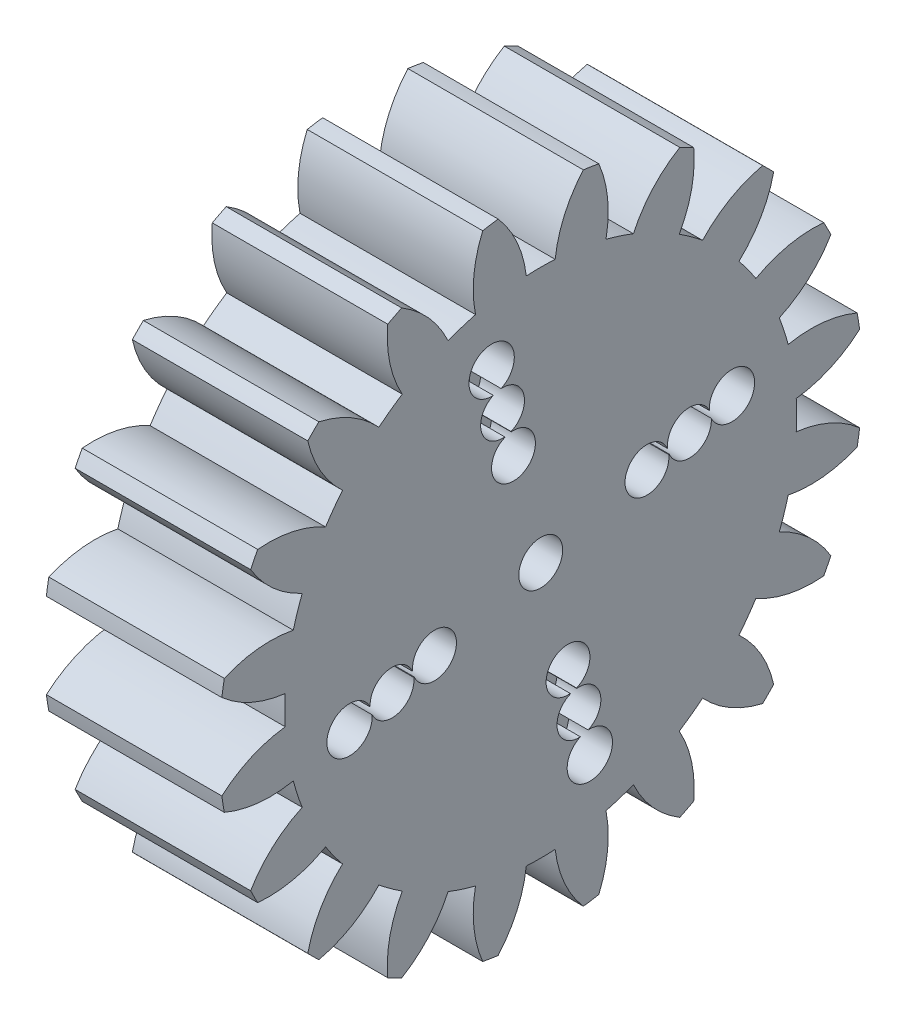
SolidWorks part; units mm, degrees
material "WhitePLA"
ref_plane "Plane1" through (0, 0, 0) normal (0, 0, 1) x (1, 0, 0)
ref_plane "Plane2" through (0, 0, 0) normal (0, 1, 0) x (1, 0, 0)
ref_plane "Plane3" through (0, 0, 0) normal (1, 0, 0) x (0, 0, -1)
sketch "HoldingSke" plane through (0, 0, 0) normal (0, 1, 0) x (1, 0, 0)
  line L0 (0, 0) -> (0.4698, -0.171)
  line L1 (-15, 0) -> (100, 0) construction
  line L2 (0, 0) -> (-2.1039, 2.3779)
  line L3 (0, 0) -> (-11.863, 4.5341)
  line L4 (0, 0) -> (8.1152, 2.9537)
  line L5 (0, 0) -> (-46.8476, -17.4728)
  line L6 (0, 0) -> (-9.9476, -6.7116)
  line L7 (-2.1039, 2.3779) -> (8.6586, 51.2059)
  line L8 (-76.2, 54.61) -> (-75.7, 54.61)
  line L9 (-71.009, 38.7566) -> (-53.1078, 45.2721)
  line L10 (-76.2, 71.12) -> (104.1128, 71.12)
  line L11 (0, 0) -> (-12, 0)
  line L12 (-76.2, 101.6) -> (-76.133, 101.6)
  line L13 (24.9733, 27.94) -> (52.9518, 28.4284)
  line L14 (24.9733, 27.94) -> (24.9743, 27.94)
  line L15 (24.9733, 27.94) -> (100.4006, 29.5858)
  line L16 (-63.627, -2) -> (-12.827, -2)
  circle A0 centre (0, 0) radius 1.5
  circle A1 centre (0, 0) radius 17.499
  circle A2 centre (0, 0) radius 37.5
  circle A3 centre (0, 0) radius 1.5
  dimension "Num_teeth" = 20
  dimension "Pitch_radius" = 180.3128
  dimension "Width" = 12
  dimension "Thickness" = 12
sketch "BasProSke" plane through (0, 0, 0) normal (0, 1, 0) x (1, 0, 0)
  line L0 (-10, 0) -> (60, 0) construction
  line L1 (0, 0) -> (0, 22)
  line L2 (0, 0) -> (12, 0)
  line L3 (12, 0) -> (12, 22)
  line L4 (12, 22) -> (0, 22)
  dimension "Thickness" = 12
  dimension "Diameter" = 44
revolve "Base-Revolve" add sketch "BasProSke" angle 360 about L0
sketch "TooCutSke" plane through (0, 0, 0) normal (1, 0, 0) x (0, 0, -1)
  line L1 (0, 0) -> (0, 107) construction
  line L2 (0, 0) -> (-1.6864, 19.9288) construction
  line L3 (0, 0) -> (-6.2409, 39.4033) construction
  line L4 (-1.6864, 19.9288) -> (-3.1204, 19.7016) construction
  arc A0 (0.9862, 17.4712) -> (-0.9862, 17.4712) centre (0, 0) ccw
  arc A1 (2.9329, 21.8293) -> (-2.9329, 21.8293) centre (0, 0) ccw
  circle A2 centre (0, 0) radius 20 construction
  circle A3 centre (0, 0) radius 18.7939 construction
  arc A4 (-0.9862, 17.4712) -> (-2.9329, 21.8293) centre (-8.9313, 16.536) ccw
  arc A5 (2.9329, 21.8293) -> (0.9862, 17.4712) centre (8.9313, 16.536) ccw
extrude "ToothCut" cut sketch "TooCutSke" along normal through all
fillet "Breaks" [suppressed] radius 0.04 tangent propagation no
fillet "RootFillets" [suppressed] radius 0.501
pattern_circular "TeethCuts" count 20 every 18 about axis through (-10, 0, 0) along (1, 0, 0) of "ToothCut", "RootFillets", "Breaks"
sketch "HubNeaOneSke" plane through (0, 0, 0) normal (-1, 0, 0) x (0, 0, 1)
  circle A0 centre (0, 0) radius 17.499
  dimension "Diameter" = 34.998
extrude "HubNearOne" [suppressed] add sketch "HubNeaOneSke" along normal blind 38.0001
sketch "HubNeaBotSke" plane through (0, 0, 0) normal (-1, 0, 0) x (0, 0, 1)
  circle A0 centre (0, 0) radius 17.499
  dimension "Diameter" = 34.998
extrude "HubNearBoth" [suppressed] add sketch "HubNeaBotSke" along normal blind 19
ref_plane "FarPln" through (12, 0, 0) normal (1, 0, 0) x (0, 0, -1)
sketch "HubFarSke" plane through (12, 0, 0) normal (1, 0, 0) x (0, 0, -1)
  circle A0 centre (0, 0) radius 17.499
  dimension "Diameter" = 34.998
extrude "HubFar" [suppressed] add sketch "HubFarSke" along normal blind 19
sketch "BorSke" plane through (0, 0, 0) normal (1, 0, 0) x (0, 0, -1)
  circle A0 centre (0, 0) radius 1.5
  dimension "Diameter" = 3
extrude "Bore" cut sketch "BorSke" along normal mid plane 100.0001
sketch "KeySke" plane through (0, 0, 0) normal (1, 0, 0) x (0, 0, -1)
  line L0 (-0.6, 0) -> (-0.6, 2)
  line L1 (-0.6, 2) -> (0.6, 2)
  line L2 (0.6, 2) -> (0.6, 0)
  line L3 (0, 0) -> (0, 34) construction
  line L4 (-0.6, 0) -> (0.6, 0)
extrude "Keyway" [suppressed] cut sketch "KeySke" along normal mid plane 100.0001
pattern_circular "Keyway2" [suppressed] count 2 every 90 about axis through (-10, 0, 0) along (1, 0, 0) reverse direction yes
sketch "Sketch1" plane through (12, 0, 0) normal (1, 0, 0) x (0, 0, -1)
  line L0 (-2.4602, 8.6778) -> (-2.4471, 8.6468)
  line L1 (-2.0331, 8.786) -> (-2.0207, 8.7563)
  circle A0 centre (3.3568, -13.076) radius 0.75
  circle A1 centre (2.6109, -10.1702) radius 0.75
  circle A2 centre (1.8649, -7.2644) radius 0.75
  circle A3 centre (-13.076, -3.3568) radius 0.75
  circle A4 centre (-10.1702, -2.6109) radius 0.75
  circle A5 centre (-7.2644, -1.8649) radius 0.75
  circle A6 centre (13.076, 3.3568) radius 0.75
  circle A7 centre (10.1702, 2.6109) radius 0.75
  circle A8 centre (7.2644, 1.8649) radius 0.75
  circle A9 centre (-1.8649, 7.2644) radius 0.75
  circle A10 centre (-2.6109, 10.1702) radius 0.75
  circle A11 centre (-3.3568, 13.076) radius 0.75
  circle A12 centre (0, 0) radius 14.25
  circle A13 centre (0, 0) radius 1.5
  arc A14 (-2.7112, 11.6669) -> (-3.2439, 11.5301) centre (-3.3568, 13.076) ccw
  arc A15 (-3.2439, 11.5301) -> (-2.4602, 8.6778) centre (-2.6109, 10.1702) ccw
  arc A16 (-2.4471, 8.6468) -> (-2.0207, 8.7563) centre (-1.8649, 7.2644) ccw
  arc A17 (-2.0331, 8.786) -> (-2.7112, 11.6669) centre (-2.6109, 10.1702) ccw
  circle A18 centre (0, 0) radius 22
  dimension "D1" = 3
  dimension "D2" = 28.5
  dimension "D3" = 1.5
  dimension "D29" = 3.1
  dimension "D30" = 3
  dimension "D33" = 44
  dimension "D4" = 4.3952
  dimension "D5" = 7.301
  dimension "D6" = 10.2067
  dimension "D7" = 14.1144
  dimension "D8" = 14.8603
  dimension "D9" = 15.6063
  dimension "D10" = 17.4712
  dimension "D11" = 19.3361
  dimension "D12" = 20.0821
  dimension "D13" = 20.828
  dimension "D14" = 24.7356
  dimension "D15" = 27.6414
  dimension "D16" = 30.5472
  dimension "D17" = 8.7303
  dimension "D18" = 11.6361
  dimension "D19" = 14.5419
  dimension "D20" = 18.4495
  dimension "D21" = 19.1955
  dimension "D22" = 19.9414
  dimension "D23" = 21.8063
  dimension "D24" = 23.6712
  dimension "D25" = 24.4172
  dimension "D26" = 25.1632
  dimension "D27" = 29.0708
  dimension "D28" = 31.9766
  dimension "D31" = 15.011
  dimension "D32" = 15.4381
  dimension "D35" = 20.3839
extrude "Cut-Extrude1" cut sketch "Sketch1" against normal up to surface (12 mm away) contours A11 | A10 | A7 | A6 | A5 | A4 | A2 | A0 | A9 | A8 | A3 | A1 region at (12, 13.076, 3.3568) region at (12, -13.076, -3.3568) region at (12, 3.3568, -13.076) region at (12, -7.2644, -1.8649) region at (12, -2.6109, 10.1702) region at (12, -1.8649, 7.2644) region at (12, 2.6109, -10.1702) region at (12, 10.1702, 2.6109) up to face at (0, 0, -1.5)
extrude "Cut-Extrude2" cut sketch "Sketch1<3>" against normal blind 3 contours L1 A17 A14 A12 A11 A15 L0 A16 A10 A9 | A12 A14 region at (12, 9.7979, 3.9659) region at (12, 14.1077, 3.6217)
sketch "Sketch1<3>" plane through (12, 0, 0) normal (1, 0, 0) x (0, 0, -1) same geometry as "Sketch1"
ref_axis "Axis1" through (12, 0, 0) along (1, 0, 0)
pattern_circular "CirPattern1" count 4 every 90 about axis through (12, 0, 0) along (1, 0, 0) of "Cut-Extrude2"
ref_axis "Axis2" through (12, 0, 0) along (1, 0, 0)
equation "' \"Module@HoldingSke\" = 6.35"
equation "' \"Num_teeth@HoldingSke\" = 12"
equation "' \"Ap@HoldingSke\" =  20"
equation "' \"Ap@HoldingSke\" = 20"
equation "' \"Width@HoldingSke\" = 0.5 * 25.4"
equation "' \"Hub_dia@HoldingSke\"= 1 * 25.4"
equation "' \"Hub_dia@HoldingSke\" = 1 * 25.4"
equation "' \"Overall_len@HoldingSke\" = 1.0 * 25.4"
equation "' \"Bore@HoldingSke\" = 0.75 * 25.4"
equation "' \"T_dim@HoldingSke\" = 0.1 * 25.4"
equation "' \"Width@KeySke\" = 0.25 * 25.4"
equation "' \"Show_teeth@HoldingSke\" = 13"
equation "' \"Backlash@HoldingSke\" = 0.009 * 25.4"
equation "' \"Addendum_fac@HoldingSke\" = 1.0"
equation "' \"Dedendum_fac@HoldingSke\" = 1.25"
equation "' \"Dedendum_add@HoldingSke\" = 0.00005 * 25.4"
equation "' \"Clearance_fac@HoldingSke\" = 0.25"
equation "\"Pitch@HoldingSke\" = 1 / \"Module@HoldingSke\""
equation "\"Overcut_dia@TooCutSke\" = (\"Num_teeth@HoldingSke\" + 2 * \"Addendum_fac@HoldingSke\") / \"Pitch@HoldingSke\" + 0.002 * 25.4"
equation "\"Pitch_dia@TooCutSke\" = \"Num_teeth@HoldingSke\" / \"Pitch@HoldingSke\""
equation "\"Base_dia@TooCutSke\" = \"Num_teeth@HoldingSke\" / \"Pitch@HoldingSke\" * cos((\"Ap@HoldingSke\"  * 3.14159265 / 180))"
equation "\"Root_dia@TooCutSke\" = (\"Num_teeth@HoldingSke\" + 2) / \"Pitch@HoldingSke\" - 2 * (\"Addendum_fac@HoldingSke\" + \"Dedendum_fac@HoldingSke\") / \"Pitch@HoldingSke\" - \"Dedendum_add@HoldingSke\" * 2"
equation "\"Half_ang@TooCutSke\" = 180 / \"Num_teeth@HoldingSke\""
equation "\"Half_CT@TooCutSke\" = \"Num_teeth@HoldingSke\" / \"Pitch@HoldingSke\" * sin((3.14159265 / 2 / \"Num_teeth@HoldingSke\")) / 2 - 7 * \"Backlash@HoldingSke\" / 4"
equation "\"Flank_rad@TooCutSke\" = \"Num_teeth@HoldingSke\" / \"Pitch@HoldingSke\" / 5"
equation "\"Radius@RootFillets\" = \"Clearance_fac@HoldingSke\" / \"Pitch@HoldingSke\" + \"Dedendum_add@HoldingSke\""
equation "\"Break_rad@Breaks\" = 0.02 / \"Pitch@HoldingSke\""
equation "\"Thickness@HoldingSke\" = \"Width@HoldingSke\""
equation "\"OAL@HoldingSke\" = \"Thickness@HoldingSke\""
equation "\"MHD@HoldingSke\" = (\"Num_teeth@HoldingSke\" + 2) / \"Pitch@HoldingSke\" - 2 * (\"Addendum_fac@HoldingSke\" + \"Dedendum_fac@HoldingSke\")  / \"Pitch@HoldingSke\" - \"Dedendum_add@HoldingSke\" * 2"
equation "\"MBD@HoldingSke\" = (\"Num_teeth@HoldingSke\" + 2) / \"Pitch@HoldingSke\" - 2 * (\"Addendum_fac@HoldingSke\" + \"Dedendum_fac@HoldingSke\")  / \"Pitch@HoldingSke\" - \"Dedendum_add@HoldingSke\" * 2 - 0.002 * 25.4"
equation "\"MHD@HoldingSke\" = ((sgn( \"MHD@HoldingSke\" - \"Hub_dia@HoldingSke\" )-1)*( \"MHD@HoldingSke\" - \"Hub_dia@HoldingSke\" ))/-2+ \"Hub_dia@HoldingSke\""
equation "\"MBD@HoldingSke\" = ((sgn( \"MBD@HoldingSke\" - \"Bore@HoldingSke\" )-1)*( \"MBD@HoldingSke\" - \"Bore@HoldingSke\" ))/-2+ \"Bore@HoldingSke\""
equation "\"OAL@HoldingSke\" = ((sgn( \"OAL@HoldingSke\" - \"Overall_len@HoldingSke\" )+1)*( \"OAL@HoldingSke\" - \"Overall_len@HoldingSke\" ))/2 + \"Overall_len@HoldingSke\" + 0.000002 * 25.4"
equation "\"Num_teeth@TeethCuts\" = int( \"Show_teeth@HoldingSke\" ) + 1"
equation "\"Num_teeth@TeethCuts\" = ((sgn( \"Num_teeth@TeethCuts\" - \"Num_teeth@HoldingSke\" )-1)*( \"Num_teeth@TeethCuts\" - \"Num_teeth@HoldingSke\" ))/-2+ \"Num_teeth@HoldingSke\""
equation "\"Num_teeth@TeethCuts\" = ((sgn( \"Num_teeth@TeethCuts\" - 2.0)+1)*( \"Num_teeth@TeethCuts\" - 2.0))/2 +2.0"
equation "\"Angle@TeethCuts\" = 360.0 / \"Num_teeth@HoldingSke\""
equation "\"Diameter@BasProSke\" = (\"Num_teeth@HoldingSke\" + 2 * \"Addendum_fac@HoldingSke\") / \"Pitch@HoldingSke\""
equation "\"Thickness@BasProSke\"  = \"Thickness@HoldingSke\""
equation "' \"Fillet_rad@BasProSke\" =  \"Thickness@HoldingSke\" * 0.05"
equation "' \"Fillet_rad@BasProSke\" = \"Thickness@HoldingSke\" * 0.05"
equation "\"MHD@HoldingSke\" = ((sgn( \"MHD@HoldingSke\" - \"Root_dia@TooCutSke\" )-1)*( \"MHD@HoldingSke\" - \"Root_dia@TooCutSke\" ))/-2+ \"Root_dia@TooCutSke\""
equation "\"Diameter@HubNeaOneSke\" = \"MHD@HoldingSke\""
equation "\"Length@HubNearOne\" = \"OAL@HoldingSke\" - \"Thickness@BasProSke\""
equation "\"Diameter@HubNeaBotSke\" = \"MHD@HoldingSke\""
equation "\"Length@HubNearBoth\" = ( \"OAL@HoldingSke\" - \"Thickness@BasProSke\" ) / 2.0"
equation "\"Thickness@FarPln\" = \"Thickness@BasProSke\""
equation "\"Diameter@HubFarSke\" = \"MHD@HoldingSke\""
equation "\"Length@HubFar\" = ( \"OAL@HoldingSke\" - \"Thickness@BasProSke\" ) / 2.0"
equation "\"Diameter@BorSke\" = \"MBD@HoldingSke\""
equation "\"D1@Bore\" = \"OAL@HoldingSke\" * 2.0"
equation "\"D1@Keyway\" = \"OAL@HoldingSke\" * 2.0"
equation "\"Offset@KeySke\" = \"T_dim@HoldingSke\" + \"MBD@HoldingSke\" / 2.0"
